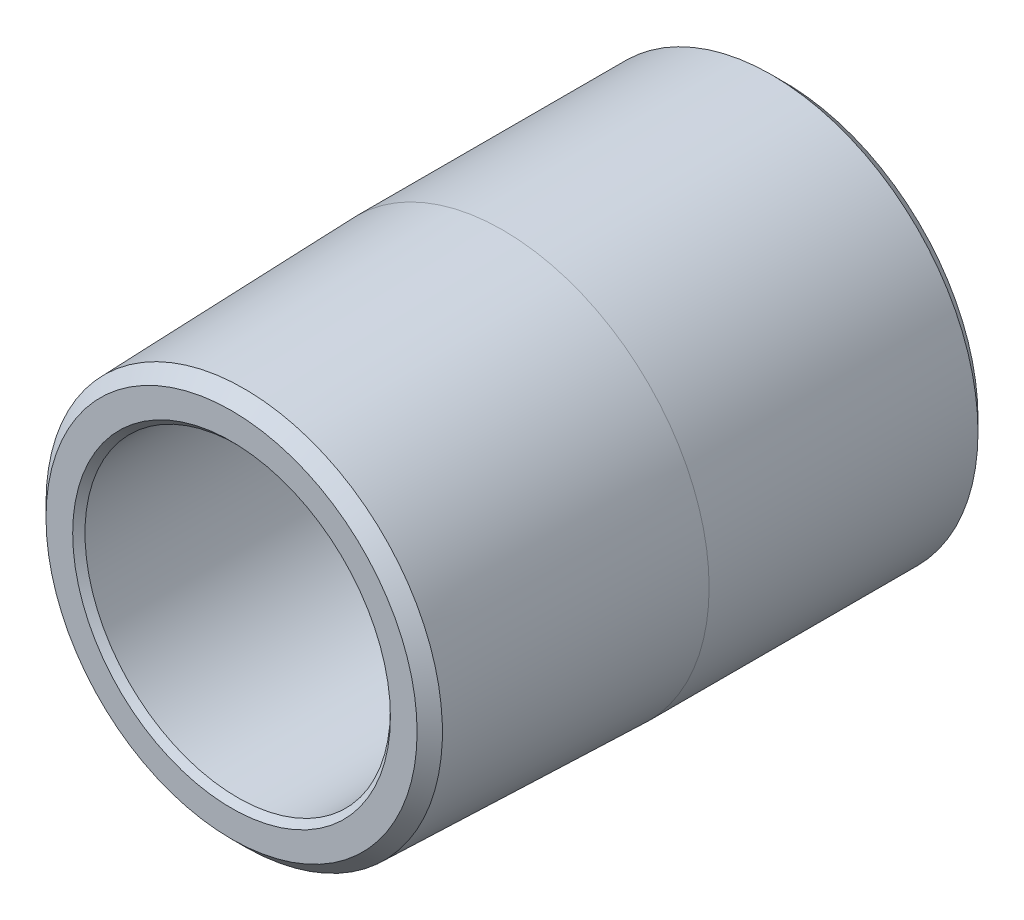
SolidWorks part; units mm, degrees
material "AISI 316  (SS)"
ref_plane "Front" through (0, 0, 0) normal (0, 0, 1) x (1, 0, 0)
ref_plane "Top" through (0, 0, 0) normal (0, 1, 0) x (1, 0, 0)
ref_plane "Side" through (0, 0, 0) normal (1, 0, 0) x (0, 0, -1)
sketch "PipeSketch" plane through (0, 0, 0) normal (0, 0, 1) x (1, 0, 0)
  circle A0 centre (0, 0) radius 10.668
  circle A1 centre (0, 0) radius 7.8994
  dimension "OuterDiameter" = 21.336
  dimension "InnerDiameter" = 15.7988
extrude "Extrusion" add sketch "PipeSketch" along normal blind 28.575
sketch "FilterSketch" plane through (0, 0, 0) normal (0, 0, 1) x (1, 0, 0)
  circle A0 centre (0, 0) radius 6.35 construction
  dimension "NominalDiameter" = 12.7
sketch "Sketch3" plane through (0, 0, 0) normal (1, 0, 0) x (0, 0, -1)
  line L0 (-28.575, 10.668) -> (-28.575, 10.2319)
  line L1 (-28.575, 10.2319) -> (-14.5415, 10.668)
  line L2 (0, 10.668) -> (-28.575, 10.668) construction
  line L3 (-14.5415, 10.668) -> (-28.575, 10.668)
  line L7 (0, -10.668) -> (0, 10.668) construction
  line L9 (0, 0) -> (-29.5419, 0) construction
  dimension "D1" = 1.78
  dimension "D2" = 14.0335
revolve "Cut-Revolve1" cut sketch "Sketch3" angle 360 about L9
chamfer "Chamfer1" distance 0.635 angle 45 2 edges at (10.668, 0, 0) (-10.2319, 0, 28.575) first distance on face at (10.668, 0, 0) first distance on face at (7.8994, 0, 28.575)
chamfer "Chamfer2" distance 0.3175 angle 45 2 edges at (7.8994, 0, 28.575) (7.8994, 0, 0)
ref_plane "Plane1" through (0, 0, 14.5415) normal (0, 0, 1) x (1, 0, 0)
ref_plane "Plane3" through (0, 0, 14.2875) normal (0, 0, 1) x (1, 0, 0)
sketch "Sketch4" plane through (0, 0, 14.5415) normal (0, 0, 1) x (1, 0, 0)
  point P0 (0, 0)
sketch "Sketch5" plane through (0, 0, 0) normal (0, 0, 1) x (1, 0, 0)
  point P0 (0, 0)
sketch "Sketch6" plane through (0, 0, 14.2875) normal (0, 0, 1) x (1, 0, 0)
  point P0 (0, 0)
other "CPoint1" parameters "Diameter"=12.7, "StubLength"=38.1
ref_axis "Axis1" through (0, 0, 24.5415) along (0, 0, -1)
other "CPoint2" parameters "Diameter"=12.7, "StubLength"=38.1
ref_axis "Axis2" through (0, 0, -10) along (0, 0, 1)
other "RPoint1"
equation "\"D1@Plane3\"= \"Length@Extrusion\" / 2"
